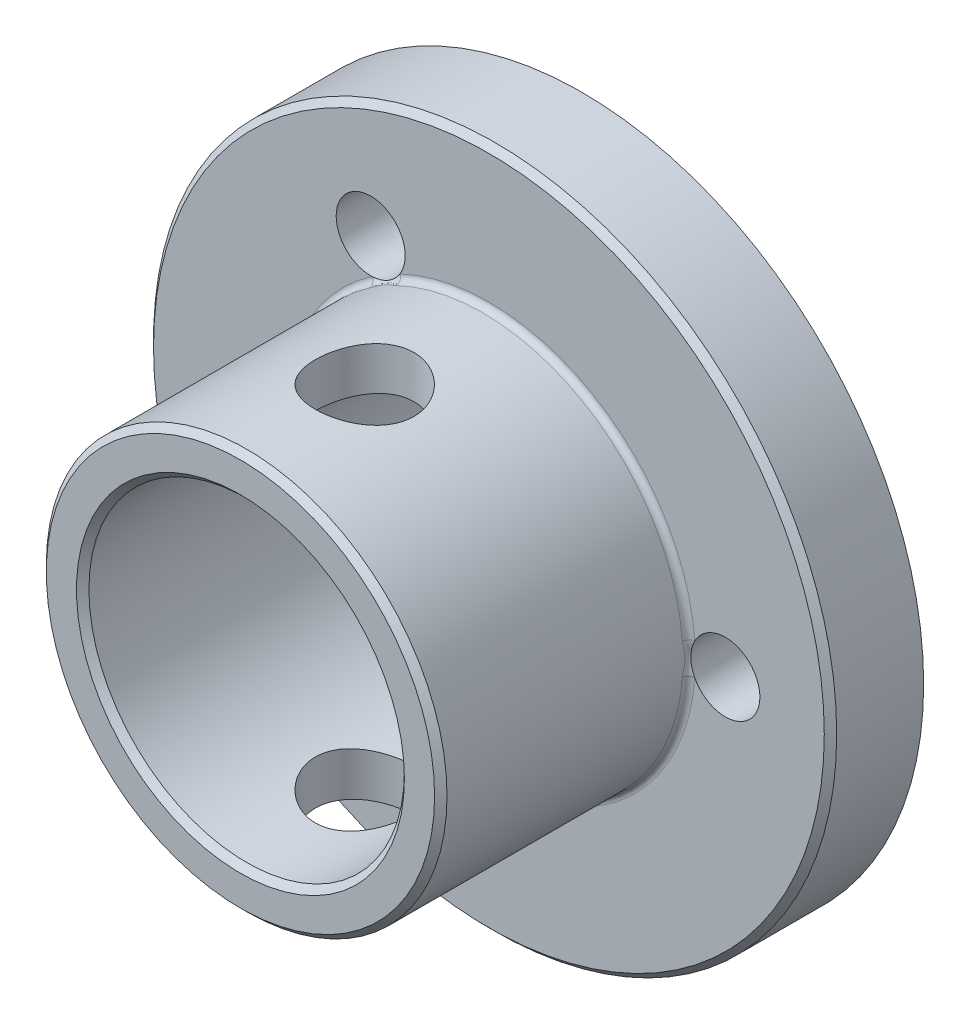
SolidWorks part; units mm, degrees
ref_plane "Front Plane" through (0, 0, 0) normal (0, 0, 1) x (1, 0, 0)
ref_plane "Top Plane" through (0, 0, 0) normal (0, 1, 0) x (1, 0, 0)
ref_plane "Right Plane" through (0, 0, 0) normal (1, 0, 0) x (0, 0, -1)
sketch "Sketch1" plane through (0, 0, 0) normal (0, 0, 1) x (1, 0, 0)
  line L0 (0, -5.9574) -> (0, 5.9574) construction
  line L2 (-31.4215, 0) -> (31.4215, 0) construction
  circle A0 centre (0, 0) radius 27.5
  circle A1 centre (-9.5171, 16.484) radius 2.7781
  circle A2 centre (19.0341, 0) radius 2.7781
  circle A3 centre (-9.5171, -16.484) radius 2.7781
  circle A4 centre (0, 0) radius 19.0341 construction
  circle A5 centre (0, 0) radius 12.7
  point P10 (-9.5171, 16.484)
  point P18 (0, 0)
  dimension "D1" = 5.5562
  dimension "D2" = 55
  dimension "D5" = 6.3341
  dimension "D3" = 25.4
  dimension "D4" = 3
extrude "Boss-Extrude1" add sketch "Sketch1" along normal blind 7.5
sketch "Sketch3" plane through (0, 0, 7.5) normal (0, 0, 1) x (1, 0, 0)
  circle A0 centre (0, 0) radius 16.129
  circle A1 centre (0, 0) radius 12.7
  circle A2 centre (0, 0) radius 12.7 construction
  dimension "D1" = 3.429
extrude "Boss-Extrude2" add sketch "Sketch3" along normal blind 20
fillet "Fillet1" radius 0.5 1 edges at (16.129, 0, 7.5)
chamfer "Chamfer1" distance 0.5 angle 45 2 edges at (12.7, 0, 27.5) (16.129, 0, 27.5)
sketch "Sketch4" plane through (0, 0, 0) normal (0, 1, 0) x (1, 0, 0)
  line L0 (0, 5.0166) -> (0, -23.8097) construction
  line L1 (-27.2201, -17.5) -> (27.6437, -17.5) construction
  line L2 (-15.629, -27.5) -> (15.629, -27.5) construction
  line L3 (-27.5, -7.5) -> (27.5, -7.5) construction
  circle A0 centre (0, -17.5) radius 3.9688
  dimension "D1" = 7.9375
  dimension "D2" = 0
extrude "Cut-Extrude3" cut sketch "Sketch4" against normal through all both and the other way through all
chamfer "Chamfer2" distance 0.5 angle 45 1 edges at (27.5, 0, 7.5)
ref_plane "Plane1" through (15.24, 0, 0) normal (1, 0, 0) x (0, 0, -1)
ref_plane "Plane2" through (-20.32, 0, 0) normal (1, 0, 0) x (0, 0, -1)
